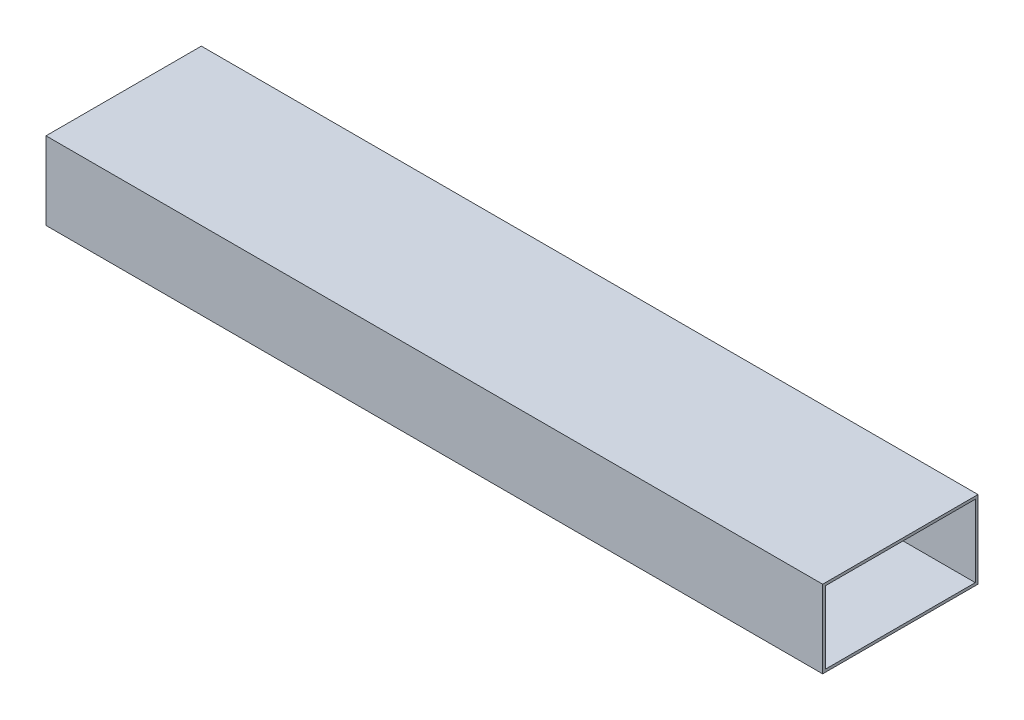
SolidWorks part; units mm, degrees
material "AISI 4130 Steel, annealed at 865C"
ref_plane "Front Plane" through (0, 0, 0) normal (0, 0, 1) x (1, 0, 0)
ref_plane "Top Plane" through (0, 0, 0) normal (0, 1, 0) x (1, 0, 0)
ref_plane "Right Plane" through (0, 0, 0) normal (1, 0, 0) x (0, 0, -1)
sketch "Sketch1" plane through (0, 0, 0) normal (1, 0, 0) x (0, 0, -1)
  line L0 (-24.511, -11.811) -> (-24.511, 11.811)
  line L1 (-25.4, -12.7) -> (25.4, -12.7)
  line L2 (-25.4, -12.7) -> (-25.4, 12.7)
  line L3 (-25.4, 12.7) -> (25.4, 12.7)
  line L4 (25.4, -12.7) -> (25.4, 12.7)
  line L5 (-25.4, -12.7) -> (25.4, 12.7) construction
  line L6 (-25.4, 12.7) -> (25.4, -12.7) construction
  line L7 (-24.511, 11.811) -> (24.511, 11.811)
  line L8 (24.511, -11.811) -> (24.511, 11.811)
  line L9 (-24.511, -11.811) -> (24.511, -11.811)
  point P0 (0, 0)
  dimension "D1" = 50.8
  dimension "D2" = 25.4
  dimension "D3" = 0.889
extrude "Boss-Extrude1" add sketch "Sketch1" along normal mid plane 254
ref_axis "Axis1" through (0, 0, 0) along (1, 0, 0)
